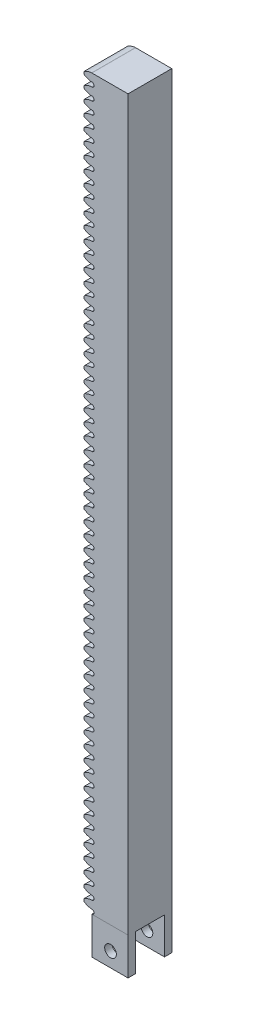
SolidWorks part; units mm, degrees
material "Plain Carbon Steel"
ref_plane "Front Plane" through (0, 0, 0) normal (0, 0, 1) x (1, 0, 0)
ref_plane "Top Plane" through (0, 0, 0) normal (0, 1, 0) x (1, 0, 0)
ref_plane "Right Plane" through (0, 0, 0) normal (1, 0, 0) x (0, 0, -1)
sketch "Sketch1" plane through (0, 0, 0) normal (0, 1, 0) x (1, 0, 0)
  line L1 (-12.4, -15) -> (12.4, -15)
  line L2 (-12.4, -15) -> (-12.4, 15)
  line L3 (-12.4, 15) -> (12.4, 15)
  line L4 (12.4, -15) -> (12.4, 15)
  line L5 (-12.4, -15) -> (12.4, 15) construction
  line L6 (-12.4, 15) -> (12.4, -15) construction
  point P0 (0, 0)
  dimension "D1" = 30
  dimension "D2" = 24.8
extrude "Boss-Extrude1" add sketch "Sketch1" along normal mid plane 525
sketch "do not delete" plane through (0, 0, 0) normal (0, 0, 1) x (1, 0, 0)
  circle A0 centre (-81.0597, 209.1285) radius 17.5
  line B0 (-46.1597, 207.5204) -> (-46.1597, 210.7365)
  line B1 (-50.1652, 211.8014) -> (-50.2795, 211.7916)
  line B2 (-50.776, 215.245) -> (-50.6636, 215.2677)
  line B3 (-52.1697, 220.3971) -> (-52.2766, 220.3555)
  line B4 (-53.726, 223.5291) -> (-53.6245, 223.5826)
  line B5 (-56.5147, 228.0799) -> (-56.6056, 228.0098)
  line B6 (-58.8903, 230.6466) -> (-58.808, 230.7265)
  line B7 (-62.8482, 234.2273) -> (-62.9156, 234.1345)
  line B8 (-65.8507, 236.0207) -> (-65.7942, 236.1206)
  line B9 (-70.657, 238.3414) -> (-70.6956, 238.2334)
  line B10 (-74.0432, 239.2163) -> (-74.0172, 239.328)
  line B11 (-79.3087, 240.0888) -> (-79.3152, 239.9743)
  line B12 (-82.8041, 239.9743) -> (-82.8106, 240.0888)
  line B13 (-88.1021, 239.328) -> (-88.0761, 239.2163)
  line B14 (-91.4237, 238.2334) -> (-91.4623, 238.3414)
  line B15 (-96.3251, 236.1206) -> (-96.2686, 236.0207)
  line B16 (-99.2037, 234.1345) -> (-99.2711, 234.2273)
  line B17 (-103.3113, 230.7265) -> (-103.229, 230.6466)
  line B18 (-105.5137, 228.0098) -> (-105.6046, 228.0799)
  line B19 (-108.4948, 223.5826) -> (-108.3933, 223.5291)
  line B20 (-109.8427, 220.3555) -> (-109.9496, 220.3971)
  line B21 (-111.4557, 215.2677) -> (-111.3433, 215.245)
  line B22 (-111.8398, 211.7916) -> (-111.9541, 211.8014)
  line B23 (-111.9541, 206.4555) -> (-111.8398, 206.4653)
  line B24 (-111.3433, 203.012) -> (-111.4557, 202.9892)
  line B25 (-109.9496, 197.8598) -> (-109.8427, 197.9014)
  line B26 (-108.3933, 194.7278) -> (-108.4948, 194.6743)
  line B27 (-105.6046, 190.177) -> (-105.5137, 190.2471)
  line B28 (-103.229, 187.6104) -> (-103.3113, 187.5304)
  line B29 (-99.2711, 184.0296) -> (-99.2037, 184.1224)
  line B30 (-96.2686, 182.2362) -> (-96.3251, 182.1363)
  line B31 (-91.4623, 179.9155) -> (-91.4237, 180.0236)
  line B32 (-88.0761, 179.0406) -> (-88.1021, 178.9289)
  line B33 (-82.8106, 178.1681) -> (-82.8041, 178.2826)
  line B34 (-79.3152, 178.2826) -> (-79.3087, 178.1681)
  line B35 (-74.0172, 178.9289) -> (-74.0432, 179.0406)
  line B36 (-70.6956, 180.0236) -> (-70.657, 179.9155)
  line B37 (-65.7942, 182.1363) -> (-65.8507, 182.2362)
  line B38 (-62.9156, 184.1224) -> (-62.8482, 184.0296)
  line B39 (-58.808, 187.5304) -> (-58.8903, 187.6104)
  line B40 (-56.6056, 190.2471) -> (-56.5147, 190.177)
  line B41 (-53.6245, 194.6743) -> (-53.726, 194.7278)
  line B42 (-52.2766, 197.9014) -> (-52.1697, 197.8598)
  line B43 (-50.6636, 202.9892) -> (-50.776, 203.012)
  line B44 (-50.2795, 206.4653) -> (-50.1652, 206.4555)
  arc B45 (-51.988, 213.1554) -> (-50.2795, 211.7916) centre (-50.4155, 213.3733) ccw
  arc B46 (-51.988, 213.1554) -> (-52.0311, 213.455) centre (-81.0597, 209.1285) ccw
  arc B47 (-50.776, 215.245) -> (-52.0311, 213.455) centre (-50.461, 213.6891) ccw
  arc B48 (-46.2345, 218.2505) -> (-46.8312, 220.2824) centre (-81.0597, 209.1285) ccw
  arc B49 (-54.3002, 221.1827) -> (-52.2766, 220.3555) centre (-52.8527, 221.8348) ccw
  arc B50 (-54.3002, 221.1827) -> (-54.4259, 221.4581) centre (-81.0597, 209.1285) ccw
  arc B51 (-53.726, 223.5291) -> (-54.4259, 221.4581) centre (-52.9853, 222.125) ccw
  arc B52 (-50.2152, 227.6923) -> (-51.3601, 229.4739) centre (-81.0597, 209.1285) ccw
  arc B53 (-58.7802, 228.2335) -> (-56.6056, 228.0098) centre (-57.5751, 229.2669) ccw
  arc B54 (-58.7802, 228.2335) -> (-58.9784, 228.4622) centre (-81.0597, 209.1285) ccw
  arc B55 (-58.8903, 230.6466) -> (-58.9784, 228.4622) centre (-57.784, 229.508) ccw
  arc B56 (-56.6946, 235.6303) -> (-58.2951, 237.0171) centre (-81.0597, 209.1285) ccw
  arc B57 (-65.0652, 233.7364) -> (-62.9156, 234.1345) centre (-64.2, 235.0675) ccw
  arc B58 (-65.0652, 233.7364) -> (-65.3198, 233.9001) centre (-81.0597, 209.1285) ccw
  arc B59 (-65.8507, 236.0207) -> (-65.3198, 233.9001) centre (-64.4684, 235.24) ccw
  arc B60 (-65.148, 241.4212) -> (-67.0744, 242.3009) centre (-81.0597, 209.1285) ccw
  arc B61 (-72.6459, 237.2458) -> (-70.6956, 238.2334) centre (-72.1908, 238.7667) ccw
  arc B62 (-72.6459, 237.2458) -> (-72.9363, 237.3311) centre (-81.0597, 209.1285) ccw
  arc B63 (-74.0432, 239.2163) -> (-72.9363, 237.3311) centre (-72.497, 238.8566) ccw
  arc B64 (-74.8904, 244.5959) -> (-76.9866, 244.8973) centre (-81.0597, 209.1285) ccw
  arc B65 (-80.9083, 238.4773) -> (-79.3152, 239.9743) centre (-80.9001, 240.0648) ccw
  arc B66 (-80.9083, 238.4773) -> (-81.211, 238.4773) centre (-81.0597, 209.1285) ccw
  arc B67 (-82.8041, 239.9743) -> (-81.211, 238.4773) centre (-81.2192, 240.0648) ccw
  arc B68 (-85.1327, 244.8973) -> (-87.2289, 244.5959) centre (-81.0597, 209.1285) ccw
  arc B69 (-89.183, 237.3311) -> (-88.0761, 239.2163) centre (-89.6223, 238.8566) ccw
  arc B70 (-89.183, 237.3311) -> (-89.4734, 237.2458) centre (-81.0597, 209.1285) ccw
  arc B71 (-91.4237, 238.2334) -> (-89.4734, 237.2458) centre (-89.9285, 238.7667) ccw
  arc B72 (-95.0449, 242.3009) -> (-96.9713, 241.4212) centre (-81.0597, 209.1285) ccw
  arc B73 (-96.7995, 233.9001) -> (-96.2686, 236.0207) centre (-97.6509, 235.24) ccw
  arc B74 (-96.7995, 233.9001) -> (-97.0541, 233.7364) centre (-81.0597, 209.1285) ccw
  arc B75 (-99.2037, 234.1345) -> (-97.0541, 233.7364) centre (-97.9193, 235.0675) ccw
  arc B76 (-103.8242, 237.0171) -> (-105.4247, 235.6303) centre (-81.0597, 209.1285) ccw
  arc B77 (-103.1409, 228.4622) -> (-103.229, 230.6466) centre (-104.3353, 229.508) ccw
  arc B78 (-103.1409, 228.4622) -> (-103.3391, 228.2335) centre (-81.0597, 209.1285) ccw
  arc B79 (-105.5137, 228.0098) -> (-103.3391, 228.2335) centre (-104.5442, 229.2669) ccw
  arc B80 (-110.7592, 229.4739) -> (-111.9041, 227.6923) centre (-81.0597, 209.1285) ccw
  arc B81 (-107.6934, 221.4581) -> (-108.3933, 223.5291) centre (-109.134, 222.125) ccw
  arc B82 (-107.6934, 221.4581) -> (-107.8191, 221.1827) centre (-81.0597, 209.1285) ccw
  arc B83 (-109.8427, 220.3555) -> (-107.8191, 221.1827) centre (-109.2666, 221.8348) ccw
  arc B84 (-115.2881, 220.2824) -> (-115.8848, 218.2505) centre (-81.0597, 209.1285) ccw
  arc B85 (-110.0882, 213.455) -> (-111.3433, 215.245) centre (-111.6584, 213.6891) ccw
  arc B86 (-110.0882, 213.455) -> (-110.1313, 213.1554) centre (-81.0597, 209.1285) ccw
  arc B87 (-111.8398, 211.7916) -> (-110.1313, 213.1554) centre (-111.7038, 213.3733) ccw
  arc B88 (-117.0441, 210.1873) -> (-117.0441, 208.0696) centre (-81.0597, 209.1285) ccw
  arc B89 (-110.1313, 205.1015) -> (-111.8398, 206.4653) centre (-111.7038, 204.8837) ccw
  arc B90 (-110.1313, 205.1015) -> (-110.0882, 204.8019) centre (-81.0597, 209.1285) ccw
  arc B91 (-111.3433, 203.012) -> (-110.0882, 204.8019) centre (-111.6584, 204.5679) ccw
  arc B92 (-115.8848, 200.0065) -> (-115.2881, 197.9745) centre (-81.0597, 209.1285) ccw
  arc B93 (-107.8191, 197.0742) -> (-109.8427, 197.9014) centre (-109.2666, 196.4222) ccw
  arc B94 (-107.8191, 197.0742) -> (-107.6934, 196.7989) centre (-81.0597, 209.1285) ccw
  arc B95 (-108.3933, 194.7278) -> (-107.6934, 196.7989) centre (-109.134, 196.132) ccw
  arc B96 (-111.9041, 190.5646) -> (-110.7592, 188.783) centre (-81.0597, 209.1285) ccw
  arc B97 (-103.3391, 190.0235) -> (-105.5137, 190.2471) centre (-104.5442, 188.9901) ccw
  arc B98 (-103.3391, 190.0235) -> (-103.1409, 189.7947) centre (-81.0597, 209.1285) ccw
  arc B99 (-103.229, 187.6104) -> (-103.1409, 189.7947) centre (-104.3353, 188.7489) ccw
  arc B100 (-105.4247, 182.6267) -> (-103.8242, 181.2398) centre (-81.0597, 209.1285) ccw
  arc B101 (-97.0541, 184.5205) -> (-99.2037, 184.1224) centre (-97.9193, 183.1894) ccw
  arc B102 (-97.0541, 184.5205) -> (-96.7995, 184.3569) centre (-81.0597, 209.1285) ccw
  arc B103 (-96.2686, 182.2362) -> (-96.7995, 184.3569) centre (-97.6509, 183.017) ccw
  arc B104 (-96.9713, 176.8358) -> (-95.0449, 175.956) centre (-81.0597, 209.1285) ccw
  arc B105 (-89.4734, 181.0111) -> (-91.4237, 180.0236) centre (-89.9285, 179.4903) ccw
  arc B106 (-89.4734, 181.0111) -> (-89.183, 180.9258) centre (-81.0597, 209.1285) ccw
  arc B107 (-88.0761, 179.0406) -> (-89.183, 180.9258) centre (-89.6223, 179.4004) ccw
  arc B108 (-87.2289, 173.661) -> (-85.1327, 173.3596) centre (-81.0597, 209.1285) ccw
  arc B109 (-81.211, 179.7797) -> (-82.8041, 178.2826) centre (-81.2192, 178.1922) ccw
  arc B110 (-81.211, 179.7797) -> (-80.9083, 179.7797) centre (-81.0597, 209.1285) ccw
  arc B111 (-79.3152, 178.2826) -> (-80.9083, 179.7797) centre (-80.9001, 178.1922) ccw
  arc B112 (-76.9866, 173.3596) -> (-74.8904, 173.661) centre (-81.0597, 209.1285) ccw
  arc B113 (-72.9363, 180.9258) -> (-74.0432, 179.0406) centre (-72.497, 179.4004) ccw
  arc B114 (-72.9363, 180.9258) -> (-72.6459, 181.0111) centre (-81.0597, 209.1285) ccw
  arc B115 (-70.6956, 180.0236) -> (-72.6459, 181.0111) centre (-72.1908, 179.4903) ccw
  arc B116 (-67.0744, 175.956) -> (-65.148, 176.8358) centre (-81.0597, 209.1285) ccw
  arc B117 (-65.3198, 184.3569) -> (-65.8507, 182.2362) centre (-64.4684, 183.017) ccw
  arc B118 (-65.3198, 184.3569) -> (-65.0652, 184.5205) centre (-81.0597, 209.1285) ccw
  arc B119 (-62.9156, 184.1224) -> (-65.0652, 184.5205) centre (-64.2, 183.1894) ccw
  arc B120 (-58.2951, 181.2398) -> (-56.6946, 182.6267) centre (-81.0597, 209.1285) ccw
  arc B121 (-58.9784, 189.7947) -> (-58.8903, 187.6104) centre (-57.784, 188.7489) ccw
  arc B122 (-58.9784, 189.7947) -> (-58.7802, 190.0235) centre (-81.0597, 209.1285) ccw
  arc B123 (-56.6056, 190.2471) -> (-58.7802, 190.0235) centre (-57.5751, 188.9901) ccw
  arc B124 (-51.3601, 188.783) -> (-50.2152, 190.5646) centre (-81.0597, 209.1285) ccw
  arc B125 (-54.4259, 196.7989) -> (-53.726, 194.7278) centre (-52.9853, 196.132) ccw
  arc B126 (-54.4259, 196.7989) -> (-54.3002, 197.0742) centre (-81.0597, 209.1285) ccw
  arc B127 (-52.2766, 197.9014) -> (-54.3002, 197.0742) centre (-52.8527, 196.4222) ccw
  arc B128 (-46.8312, 197.9745) -> (-46.2345, 200.0065) centre (-81.0597, 209.1285) ccw
  arc B129 (-52.0311, 204.8019) -> (-50.776, 203.012) centre (-50.461, 204.5679) ccw
  arc B130 (-52.0311, 204.8019) -> (-51.988, 205.1015) centre (-81.0597, 209.1285) ccw
  arc B131 (-50.2795, 206.4653) -> (-51.988, 205.1015) centre (-50.4155, 204.8837) ccw
  spline B132 degree 5 poles (-46.1597, 210.7365) (-46.3289, 210.8147) (-46.5562, 210.9157) (-46.8422, 211.0359) (-47.202, 211.1762) (-47.6072, 211.3178) (-47.8704, 211.4029) (-48.1342, 211.4814) (-48.3544, 211.5414) (-48.5602, 211.5938) (-48.7368, 211.6345) (-48.9429, 211.6775) (-49.105, 211.7084) (-49.2819, 211.7383) (-49.4441, 211.7612) (-49.6063, 211.7784) (-49.7684, 211.7934) (-49.9157, 211.8055) (-50.0333, 211.809) (-50.1066, 211.8065) (-50.1652, 211.8014) knots 0 0 0 0 0 0 0.168282 0.225425 0.282568 0.353997 0.396854 0.425425 0.482568 0.496854 0.553997 0.568282 0.625425 0.639711 0.668282 0.711139 0.725425 0.782568 0.782568 0.782568 0.782568 0.782568 0.782568 weights 1 1 1 1 1 1 1 1 1 1 1 1 1 1 1 1 1 1 1 1 1
  spline B133 degree 5 poles (-50.6636, 215.2677) (-50.606, 215.2794) (-50.5349, 215.2977) (-50.437, 215.3296) (-50.3127, 215.3765) (-50.175, 215.4309) (-50.0378, 215.4866) (-49.9015, 215.5458) (-49.7396, 215.6223) (-49.579, 215.7033) (-49.3929, 215.8014) (-49.2082, 215.9037) (-49.0123, 216.0194) (-48.818, 216.139) (-48.574, 216.2965) (-48.3074, 216.4787) (-48.0315, 216.6776) (-47.7101, 216.9237) (-47.3817, 217.1908) (-47.0702, 217.4583) (-46.7755, 217.7249) (-46.5433, 217.945) (-46.3826, 218.1022) (-46.28, 218.2047) (-46.2345, 218.2505) knots 0 0 0 0 0 0 0.057143 0.071429 0.1 0.128571 0.142857 0.2 0.214286 0.271429 0.3 0.342857 0.4 0.428571 0.485714 0.571429 0.642857 0.714286 0.8 0.871429 0.942857 1 1 1 1 1 1 weights 1 1 1 1 1 1 1 1 1 1 1 1 1 1 1 1 1 1 1 1 1 1 1 1 1
  spline B134 degree 5 poles (-46.8312, 220.2824) (-47.0359, 220.3277) (-47.3034, 220.3829) (-47.6333, 220.4444) (-48.0409, 220.5098) (-48.525, 220.5717) (-48.8674, 220.6073) (-49.2241, 220.6357) (-49.5637, 220.6534) (-49.8556, 220.6612) (-50.1308, 220.6622) (-50.359, 220.6578) (-50.5712, 220.65) (-50.7521, 220.6394) (-50.962, 220.6226) (-51.1263, 220.6065) (-51.3044, 220.5854) (-51.4665, 220.5617) (-51.6269, 220.5325) (-51.7867, 220.5013) (-51.9314, 220.4713) (-52.0452, 220.4416) (-52.1149, 220.4185) (-52.1697, 220.3971) knots 0 0 0 0 0 0 0.185714 0.242857 0.3 0.371429 0.442857 0.5 0.571429 0.614286 0.642857 0.7 0.714286 0.771429 0.785714 0.842857 0.857143 0.885714 0.928571 0.942857 1 1 1 1 1 1 weights 1 1 1 1 1 1 1 1 1 1 1 1 1 1 1 1 1 1 1 1 1 1 1 1
  spline B135 degree 5 poles (-53.6245, 223.5826) (-53.5725, 223.6101) (-53.5094, 223.6476) (-53.4245, 223.7058) (-53.3184, 223.7858) (-53.2017, 223.8768) (-53.0856, 223.9689) (-52.9716, 224.0641) (-52.8378, 224.1831) (-52.7065, 224.3061) (-52.5556, 224.4527) (-52.4072, 224.6029) (-52.2519, 224.769) (-52.0991, 224.9386) (-51.9093, 225.1584) (-51.7049, 225.4083) (-51.4962, 225.6769) (-51.2572, 226.0036) (-51.0173, 226.3524) (-50.7939, 226.6968) (-50.5861, 227.0356) (-50.4254, 227.3122) (-50.3155, 227.5084) (-50.2459, 227.6356) (-50.2152, 227.6923) knots 0 0 0 0 0 0 0.057143 0.071429 0.1 0.128571 0.142857 0.2 0.214286 0.271429 0.3 0.342857 0.4 0.428571 0.485714 0.571429 0.642857 0.714286 0.8 0.871429 0.942857 1 1 1 1 1 1 weights 1 1 1 1 1 1 1 1 1 1 1 1 1 1 1 1 1 1 1 1 1 1 1 1 1
  spline B136 degree 5 poles (-51.3601, 229.4739) (-51.5693, 229.4597) (-51.8415, 229.4373) (-52.1754, 229.4033) (-52.5849, 229.3513) (-53.0668, 229.2742) (-53.4054, 229.2119) (-53.7556, 229.1387) (-54.0864, 229.06) (-54.3687, 228.9853) (-54.6331, 228.9087) (-54.8508, 228.8401) (-55.0522, 228.7729) (-55.2228, 228.7118) (-55.4195, 228.6365) (-55.5725, 228.5748) (-55.7375, 228.5043) (-55.8863, 228.4359) (-56.0321, 228.3627) (-56.1766, 228.2877) (-56.307, 228.2182) (-56.4078, 228.1576) (-56.4681, 228.1158) (-56.5147, 228.0799) knots 0 0 0 0 0 0 0.185714 0.242857 0.3 0.371429 0.442857 0.5 0.571429 0.614286 0.642857 0.7 0.714286 0.771429 0.785714 0.842857 0.857143 0.885714 0.928571 0.942857 1 1 1 1 1 1 weights 1 1 1 1 1 1 1 1 1 1 1 1 1 1 1 1 1 1 1 1 1 1 1 1
  spline B137 degree 5 poles (-58.808, 230.7265) (-58.7658, 230.7675) (-58.7159, 230.8213) (-58.6508, 230.901) (-58.5716, 231.0077) (-58.4852, 231.1279) (-58.3998, 231.2489) (-58.3172, 231.3724) (-58.2224, 231.5243) (-58.1311, 231.6793) (-58.0276, 231.8624) (-57.9275, 232.0484) (-57.8252, 232.2515) (-57.7264, 232.4573) (-57.6063, 232.7217) (-57.4806, 233.0191) (-57.356, 233.3356) (-57.2187, 233.7164) (-57.0868, 234.1187) (-56.9694, 234.5121) (-56.8656, 234.8956) (-56.7892, 235.2063) (-56.739, 235.4255) (-56.7081, 235.5672) (-56.6946, 235.6303) knots 0 0 0 0 0 0 0.057143 0.071429 0.1 0.128571 0.142857 0.2 0.214286 0.271429 0.3 0.342857 0.4 0.428571 0.485714 0.571429 0.642857 0.714286 0.8 0.871429 0.942857 1 1 1 1 1 1 weights 1 1 1 1 1 1 1 1 1 1 1 1 1 1 1 1 1 1 1 1 1 1 1 1 1
  spline B138 degree 5 poles (-58.2951, 237.0171) (-58.4918, 236.9445) (-58.7467, 236.8463) (-59.0575, 236.7196) (-59.4358, 236.5544) (-59.8764, 236.3447) (-60.1838, 236.1895) (-60.4992, 236.0206) (-60.7944, 235.8518) (-61.0442, 235.7006) (-61.2763, 235.5527) (-61.4658, 235.4256) (-61.6402, 235.3043) (-61.7866, 235.1976) (-61.9541, 235.0699) (-62.0836, 234.9676) (-62.2221, 234.8535) (-62.3456, 234.746) (-62.4648, 234.6347) (-62.5823, 234.522) (-62.6878, 234.4186) (-62.7675, 234.332) (-62.8136, 234.2749) (-62.8482, 234.2273) knots 0 0 0 0 0 0 0.185714 0.242857 0.3 0.371429 0.442857 0.5 0.571429 0.614286 0.642857 0.7 0.714286 0.771429 0.785714 0.842857 0.857143 0.885714 0.928571 0.942857 1 1 1 1 1 1 weights 1 1 1 1 1 1 1 1 1 1 1 1 1 1 1 1 1 1 1 1 1 1 1 1
  spline B139 degree 5 poles (-65.7942, 236.1206) (-65.7653, 236.1719) (-65.7325, 236.2375) (-65.6926, 236.3324) (-65.6466, 236.4571) (-65.5976, 236.5967) (-65.5498, 236.7369) (-65.5053, 236.8787) (-65.4571, 237.0512) (-65.4131, 237.2255) (-65.3654, 237.4304) (-65.3218, 237.637) (-65.2809, 237.8608) (-65.244, 238.086) (-65.2033, 238.3736) (-65.1664, 238.6943) (-65.1361, 239.0331) (-65.1116, 239.4372) (-65.0984, 239.8603) (-65.0966, 240.2708) (-65.105, 240.6681) (-65.1193, 240.9877) (-65.1329, 241.2122) (-65.1432, 241.3568) (-65.148, 241.4212) knots 0 0 0 0 0 0 0.057143 0.071429 0.1 0.128571 0.142857 0.2 0.214286 0.271429 0.3 0.342857 0.4 0.428571 0.485714 0.571429 0.642857 0.714286 0.8 0.871429 0.942857 1 1 1 1 1 1 weights 1 1 1 1 1 1 1 1 1 1 1 1 1 1 1 1 1 1 1 1 1 1 1 1 1
  spline B140 degree 5 poles (-67.0744, 242.3009) (-67.2427, 242.1759) (-67.4595, 242.0098) (-67.7221, 241.8007) (-68.0384, 241.5356) (-68.4022, 241.2102) (-68.6534, 240.9748) (-68.9084, 240.7238) (-69.1441, 240.4787) (-69.3412, 240.2633) (-69.5222, 240.0559) (-69.6683, 239.8806) (-69.8014, 239.7151) (-69.9118, 239.5714) (-70.0366, 239.4018) (-70.132, 239.2671) (-70.2327, 239.1187) (-70.3209, 238.9806) (-70.4039, 238.8403) (-70.4849, 238.6991) (-70.5571, 238.5701) (-70.6091, 238.4646) (-70.6373, 238.3968) (-70.657, 238.3414) knots 0 0 0 0 0 0 0.185714 0.242857 0.3 0.371429 0.442857 0.5 0.571429 0.614286 0.642857 0.7 0.714286 0.771429 0.785714 0.842857 0.857143 0.885714 0.928571 0.942857 1 1 1 1 1 1 weights 1 1 1 1 1 1 1 1 1 1 1 1 1 1 1 1 1 1 1 1 1 1 1 1
  spline B141 degree 5 poles (-74.0172, 239.328) (-74.0038, 239.3853) (-73.9909, 239.4576) (-73.9793, 239.5599) (-73.9703, 239.6924) (-73.9626, 239.8402) (-73.9562, 239.9882) (-73.9535, 240.1368) (-73.9558, 240.3158) (-73.9628, 240.4955) (-73.9747, 240.7056) (-73.9911, 240.9161) (-74.0149, 241.1423) (-74.043, 241.3688) (-74.0849, 241.6562) (-74.1399, 241.9743) (-74.2062, 242.308) (-74.2966, 242.7025) (-74.4031, 243.1123) (-74.5171, 243.5067) (-74.6371, 243.8855) (-74.7408, 244.1881) (-74.8171, 244.3997) (-74.8677, 244.5356) (-74.8904, 244.5959) knots 0 0 0 0 0 0 0.057143 0.071429 0.1 0.128571 0.142857 0.2 0.214286 0.271429 0.3 0.342857 0.4 0.428571 0.485714 0.571429 0.642857 0.714286 0.8 0.871429 0.942857 1 1 1 1 1 1 weights 1 1 1 1 1 1 1 1 1 1 1 1 1 1 1 1 1 1 1 1 1 1 1 1 1
  spline B142 degree 5 poles (-76.9866, 244.8973) (-77.1129, 244.7299) (-77.2742, 244.5095) (-77.4672, 244.2349) (-77.696, 243.8914) (-77.9534, 243.4767) (-78.128, 243.18) (-78.302, 242.8674) (-78.4592, 242.5658) (-78.5876, 242.3036) (-78.7028, 242.0536) (-78.7936, 241.8442) (-78.8747, 241.648) (-78.9402, 241.479) (-79.0121, 241.2811) (-79.0657, 241.125) (-79.1205, 240.9542) (-79.1662, 240.7969) (-79.2064, 240.6388) (-79.2443, 240.4805) (-79.2772, 240.3364) (-79.2974, 240.2205) (-79.3053, 240.1476) (-79.3087, 240.0888) knots 0 0 0 0 0 0 0.185714 0.242857 0.3 0.371429 0.442857 0.5 0.571429 0.614286 0.642857 0.7 0.714286 0.771429 0.785714 0.842857 0.857143 0.885714 0.928571 0.942857 1 1 1 1 1 1 weights 1 1 1 1 1 1 1 1 1 1 1 1 1 1 1 1 1 1 1 1 1 1 1 1
  spline B143 degree 5 poles (-82.8106, 240.0888) (-82.814, 240.1476) (-82.8219, 240.2205) (-82.8396, 240.3219) (-82.8683, 240.4517) (-82.9026, 240.5956) (-82.9381, 240.7394) (-82.9774, 240.8828) (-83.0301, 241.0539) (-83.0874, 241.2244) (-83.158, 241.4225) (-83.233, 241.6199) (-83.3196, 241.8303) (-83.4104, 242.0397) (-83.5315, 242.3036) (-83.6739, 242.5934) (-83.8316, 242.8948) (-84.0294, 243.2479) (-84.2471, 243.6111) (-84.4675, 243.9574) (-84.6894, 244.287) (-84.8742, 244.5482) (-85.007, 244.7297) (-85.0938, 244.8458) (-85.1327, 244.8973) knots 0 0 0 0 0 0 0.057143 0.071429 0.1 0.128571 0.142857 0.2 0.214286 0.271429 0.3 0.342857 0.4 0.428571 0.485714 0.571429 0.642857 0.714286 0.8 0.871429 0.942857 1 1 1 1 1 1 weights 1 1 1 1 1 1 1 1 1 1 1 1 1 1 1 1 1 1 1 1 1 1 1 1 1
  spline B144 degree 5 poles (-87.2289, 244.5959) (-87.3029, 244.3997) (-87.3955, 244.1428) (-87.5033, 243.825) (-87.6261, 243.4309) (-87.7562, 242.9605) (-87.8402, 242.6266) (-87.9191, 242.2776) (-87.9849, 241.944) (-88.0342, 241.6562) (-88.0744, 241.3839) (-88.1025, 241.1574) (-88.125, 240.9463) (-88.1402, 240.7657) (-88.1534, 240.5555) (-88.1609, 240.3907) (-88.1654, 240.2113) (-88.1649, 240.0475) (-88.1589, 239.8846) (-88.1507, 239.722) (-88.1417, 239.5745) (-88.1284, 239.4576) (-88.1155, 239.3853) (-88.1021, 239.328) knots 0 0 0 0 0 0 0.185714 0.242857 0.3 0.371429 0.442857 0.5 0.571429 0.614286 0.642857 0.7 0.714286 0.771429 0.785714 0.842857 0.857143 0.885714 0.928571 0.942857 1 1 1 1 1 1 weights 1 1 1 1 1 1 1 1 1 1 1 1 1 1 1 1 1 1 1 1 1 1 1 1
  spline B145 degree 5 poles (-91.4623, 238.3414) (-91.482, 238.3968) (-91.5102, 238.4646) (-91.5557, 238.5569) (-91.6199, 238.6733) (-91.6933, 238.8018) (-91.7679, 238.9297) (-91.8459, 239.0562) (-91.9447, 239.2056) (-92.0477, 239.353) (-92.1713, 239.5232) (-92.2989, 239.6915) (-92.4412, 239.8689) (-92.5873, 240.0443) (-92.7779, 240.2634) (-92.9962, 240.5013) (-93.2324, 240.7461) (-93.5217, 241.0292) (-93.8328, 241.3163) (-94.1419, 241.5864) (-94.4477, 241.8402) (-94.6986, 242.0387) (-94.8771, 242.1755) (-94.9931, 242.2624) (-95.0449, 242.3009) knots 0 0 0 0 0 0 0.057143 0.071429 0.1 0.128571 0.142857 0.2 0.214286 0.271429 0.3 0.342857 0.4 0.428571 0.485714 0.571429 0.642857 0.714286 0.8 0.871429 0.942857 1 1 1 1 1 1 weights 1 1 1 1 1 1 1 1 1 1 1 1 1 1 1 1 1 1 1 1 1 1 1 1 1
  spline B146 degree 5 poles (-96.9713, 241.4212) (-96.987, 241.2121) (-97.0035, 240.9395) (-97.0174, 240.6041) (-97.0242, 240.1914) (-97.0166, 239.7034) (-97.0031, 239.3594) (-96.9804, 239.0023) (-96.9496, 238.6637) (-96.9158, 238.3736) (-96.8776, 238.1011) (-96.8408, 237.8758) (-96.8029, 237.6669) (-96.7667, 237.4893) (-96.7201, 237.284) (-96.6808, 237.1237) (-96.6346, 236.9503) (-96.588, 236.7933) (-96.5364, 236.6386) (-96.4827, 236.4849) (-96.4324, 236.346) (-96.3868, 236.2375) (-96.354, 236.1719) (-96.3251, 236.1206) knots 0 0 0 0 0 0 0.185714 0.242857 0.3 0.371429 0.442857 0.5 0.571429 0.614286 0.642857 0.7 0.714286 0.771429 0.785714 0.842857 0.857143 0.885714 0.928571 0.942857 1 1 1 1 1 1 weights 1 1 1 1 1 1 1 1 1 1 1 1 1 1 1 1 1 1 1 1 1 1 1 1
  spline B147 degree 5 poles (-99.2711, 234.2273) (-99.3057, 234.2749) (-99.3518, 234.332) (-99.4215, 234.4078) (-99.5158, 234.5014) (-99.6225, 234.604) (-99.7301, 234.7057) (-99.8406, 234.8051) (-99.9775, 234.9206) (-100.1179, 235.033) (-100.2844, 235.1615) (-100.4542, 235.287) (-100.6408, 235.4171) (-100.8304, 235.5443) (-101.075, 235.7008) (-101.3514, 235.8675) (-101.647, 236.0359) (-102.0044, 236.226) (-102.3838, 236.4138) (-102.7565, 236.586) (-103.1214, 236.7433) (-103.418, 236.8631) (-103.6279, 236.944) (-103.7637, 236.9948) (-103.8242, 237.0171) knots 0 0 0 0 0 0 0.057143 0.071429 0.1 0.128571 0.142857 0.2 0.214286 0.271429 0.3 0.342857 0.4 0.428571 0.485714 0.571429 0.642857 0.714286 0.8 0.871429 0.942857 1 1 1 1 1 1 weights 1 1 1 1 1 1 1 1 1 1 1 1 1 1 1 1 1 1 1 1 1 1 1 1 1
  spline B148 degree 5 poles (-105.4247, 235.6303) (-105.3809, 235.4252) (-105.3199, 235.159) (-105.2387, 234.8333) (-105.129, 234.4354) (-104.9842, 233.9694) (-104.8743, 233.6431) (-104.752, 233.3068) (-104.627, 232.9906) (-104.5129, 232.7218) (-104.3994, 232.471) (-104.3006, 232.2653) (-104.2054, 232.0755) (-104.1206, 231.9154) (-104.0181, 231.7314) (-103.9352, 231.5887) (-103.842, 231.4354) (-103.7531, 231.2978) (-103.6599, 231.164) (-103.5651, 231.0316) (-103.4778, 230.9124) (-103.4034, 230.8213) (-103.3535, 230.7675) (-103.3113, 230.7265) knots 0 0 0 0 0 0 0.185714 0.242857 0.3 0.371429 0.442857 0.5 0.571429 0.614286 0.642857 0.7 0.714286 0.771429 0.785714 0.842857 0.857143 0.885714 0.928571 0.942857 1 1 1 1 1 1 weights 1 1 1 1 1 1 1 1 1 1 1 1 1 1 1 1 1 1 1 1 1 1 1 1
  spline B149 degree 5 poles (-105.6046, 228.0799) (-105.6512, 228.1158) (-105.7115, 228.1576) (-105.7997, 228.2106) (-105.9166, 228.2739) (-106.0478, 228.3423) (-106.1798, 228.4096) (-106.3138, 228.4738) (-106.4777, 228.546) (-106.644, 228.6143) (-106.84, 228.6907) (-107.0383, 228.7633) (-107.254, 228.8356) (-107.4717, 228.9042) (-107.7505, 228.9854) (-108.0627, 229.0676) (-108.3938, 229.1458) (-108.7902, 229.2275) (-109.2072, 229.3009) (-109.6133, 229.361) (-110.0077, 229.4092) (-110.3261, 229.4406) (-110.5502, 229.4591) (-110.6948, 229.4695) (-110.7592, 229.4739) knots 0 0 0 0 0 0 0.057143 0.071429 0.1 0.128571 0.142857 0.2 0.214286 0.271429 0.3 0.342857 0.4 0.428571 0.485714 0.571429 0.642857 0.714286 0.8 0.871429 0.942857 1 1 1 1 1 1 weights 1 1 1 1 1 1 1 1 1 1 1 1 1 1 1 1 1 1 1 1 1 1 1 1 1
  spline B150 degree 5 poles (-111.9041, 227.6923) (-111.8043, 227.5079) (-111.6709, 227.2697) (-111.5012, 226.98) (-111.2838, 226.6291) (-111.0135, 226.2228) (-110.8162, 225.9407) (-110.6041, 225.6525) (-110.3951, 225.3843) (-110.2099, 225.1586) (-110.0304, 224.9499) (-109.8776, 224.7804) (-109.7328, 224.6251) (-109.6063, 224.4953) (-109.4561, 224.3477) (-109.3364, 224.2341) (-109.2038, 224.1133) (-109.0797, 224.0063) (-108.9526, 223.9042) (-108.8243, 223.8039) (-108.7069, 223.7141) (-108.6099, 223.6476) (-108.5468, 223.6101) (-108.4948, 223.5826) knots 0 0 0 0 0 0 0.185714 0.242857 0.3 0.371429 0.442857 0.5 0.571429 0.614286 0.642857 0.7 0.714286 0.771429 0.785714 0.842857 0.857143 0.885714 0.928571 0.942857 1 1 1 1 1 1 weights 1 1 1 1 1 1 1 1 1 1 1 1 1 1 1 1 1 1 1 1 1 1 1 1
  spline B151 degree 5 poles (-109.9496, 220.3971) (-110.0044, 220.4185) (-110.0741, 220.4416) (-110.1737, 220.4676) (-110.3036, 220.4954) (-110.4488, 220.524) (-110.5944, 220.5514) (-110.741, 220.5752) (-110.9186, 220.5984) (-111.0975, 220.6171) (-111.3071, 220.6351) (-111.5178, 220.6489) (-111.7451, 220.6576) (-111.9733, 220.662) (-112.2637, 220.6614) (-112.5864, 220.6522) (-112.9261, 220.6341) (-113.3295, 220.6008) (-113.7502, 220.5537) (-114.1568, 220.497) (-114.5489, 220.4321) (-114.8632, 220.3725) (-115.0834, 220.3271) (-115.2251, 220.2964) (-115.2881, 220.2824) knots 0 0 0 0 0 0 0.057143 0.071429 0.1 0.128571 0.142857 0.2 0.214286 0.271429 0.3 0.342857 0.4 0.428571 0.485714 0.571429 0.642857 0.714286 0.8 0.871429 0.942857 1 1 1 1 1 1 weights 1 1 1 1 1 1 1 1 1 1 1 1 1 1 1 1 1 1 1 1 1 1 1 1 1
  spline B152 degree 5 poles (-115.8848, 218.2505) (-115.737, 218.1016) (-115.5419, 217.9107) (-115.2975, 217.6805) (-114.99, 217.4051) (-114.6162, 217.0914) (-114.3474, 216.8763) (-114.0627, 216.6596) (-113.7866, 216.4611) (-113.5453, 216.2967) (-113.3143, 216.1471) (-113.1199, 216.0274) (-112.9372, 215.9192) (-112.7793, 215.8303) (-112.5936, 215.731) (-112.4467, 215.6557) (-112.2854, 215.5772) (-112.1363, 215.5095) (-111.9855, 215.4473) (-111.8342, 215.3872) (-111.6963, 215.3342) (-111.5845, 215.2977) (-111.5134, 215.2794) (-111.4557, 215.2677) knots 0 0 0 0 0 0 0.185714 0.242857 0.3 0.371429 0.442857 0.5 0.571429 0.614286 0.642857 0.7 0.714286 0.771429 0.785714 0.842857 0.857143 0.885714 0.928571 0.942857 1 1 1 1 1 1 weights 1 1 1 1 1 1 1 1 1 1 1 1 1 1 1 1 1 1 1 1 1 1 1 1
  spline B153 degree 5 poles (-111.9541, 211.8014) (-112.0127, 211.8065) (-112.086, 211.809) (-112.1889, 211.8059) (-112.3215, 211.7959) (-112.4688, 211.7825) (-112.6162, 211.7678) (-112.7637, 211.7493) (-112.9406, 211.7216) (-113.1174, 211.6891) (-113.3237, 211.6474) (-113.5297, 211.6012) (-113.7502, 211.5455) (-113.9704, 211.4854) (-114.2489, 211.4031) (-114.556, 211.3033) (-114.8768, 211.1902) (-115.2545, 211.0446) (-115.6449, 210.8809) (-116.019, 210.7119) (-116.3769, 210.5392) (-116.6617, 210.3935) (-116.8603, 210.2878) (-116.9876, 210.2185) (-117.0441, 210.1873) knots 0 0 0 0 0 0 0.057143 0.071429 0.1 0.128571 0.142857 0.2 0.214286 0.271429 0.3 0.342857 0.4 0.428571 0.485714 0.571429 0.642857 0.714286 0.8 0.871429 0.942857 1 1 1 1 1 1 weights 1 1 1 1 1 1 1 1 1 1 1 1 1 1 1 1 1 1 1 1 1 1 1 1 1
  spline B154 degree 5 poles (-117.0441, 208.0696) (-116.8604, 207.9684) (-116.6193, 207.8402) (-116.32, 207.6882) (-115.9474, 207.5106) (-115.5004, 207.3148) (-115.1818, 207.1842) (-114.8476, 207.0565) (-114.5268, 206.9438) (-114.2489, 206.8541) (-113.9851, 206.7756) (-113.7649, 206.7155) (-113.5591, 206.6632) (-113.3825, 206.6224) (-113.1764, 206.5794) (-113.0143, 206.5486) (-112.8374, 206.5186) (-112.6752, 206.4957) (-112.513, 206.4785) (-112.3509, 206.4635) (-112.2036, 206.4514) (-112.086, 206.4479) (-112.0127, 206.4505) (-111.9541, 206.4555) knots 0 0 0 0 0 0 0.185714 0.242857 0.3 0.371429 0.442857 0.5 0.571429 0.614286 0.642857 0.7 0.714286 0.771429 0.785714 0.842857 0.857143 0.885714 0.928571 0.942857 1 1 1 1 1 1 weights 1 1 1 1 1 1 1 1 1 1 1 1 1 1 1 1 1 1 1 1 1 1 1 1
  spline B155 degree 5 poles (-111.4557, 202.9892) (-111.5134, 202.9775) (-111.5845, 202.9593) (-111.6823, 202.9273) (-111.8066, 202.8804) (-111.9443, 202.826) (-112.0815, 202.7704) (-112.2178, 202.7111) (-112.3797, 202.6346) (-112.5403, 202.5536) (-112.7264, 202.4555) (-112.9111, 202.3532) (-113.107, 202.2376) (-113.3014, 202.1179) (-113.5453, 201.9604) (-113.8119, 201.7782) (-114.0878, 201.5793) (-114.4092, 201.3332) (-114.7376, 201.0661) (-115.0491, 200.7986) (-115.3438, 200.5321) (-115.576, 200.312) (-115.7367, 200.1547) (-115.8393, 200.0523) (-115.8848, 200.0065) knots 0 0 0 0 0 0 0.057143 0.071429 0.1 0.128571 0.142857 0.2 0.214286 0.271429 0.3 0.342857 0.4 0.428571 0.485714 0.571429 0.642857 0.714286 0.8 0.871429 0.942857 1 1 1 1 1 1 weights 1 1 1 1 1 1 1 1 1 1 1 1 1 1 1 1 1 1 1 1 1 1 1 1 1
  spline B156 degree 5 poles (-115.2881, 197.9745) (-115.0834, 197.9292) (-114.8159, 197.874) (-114.486, 197.8126) (-114.0784, 197.7471) (-113.5943, 197.6852) (-113.2519, 197.6496) (-112.8952, 197.6212) (-112.5556, 197.6036) (-112.2637, 197.5957) (-111.9885, 197.5947) (-111.7603, 197.5991) (-111.5481, 197.6069) (-111.3672, 197.6175) (-111.1573, 197.6344) (-110.9931, 197.6504) (-110.8149, 197.6715) (-110.6528, 197.6953) (-110.4924, 197.7244) (-110.3326, 197.7557) (-110.1879, 197.7856) (-110.0741, 197.8154) (-110.0044, 197.8385) (-109.9496, 197.8598) knots 0 0 0 0 0 0 0.185714 0.242857 0.3 0.371429 0.442857 0.5 0.571429 0.614286 0.642857 0.7 0.714286 0.771429 0.785714 0.842857 0.857143 0.885714 0.928571 0.942857 1 1 1 1 1 1 weights 1 1 1 1 1 1 1 1 1 1 1 1 1 1 1 1 1 1 1 1 1 1 1 1
  spline B157 degree 5 poles (-108.4948, 194.6743) (-108.5468, 194.6469) (-108.6099, 194.6093) (-108.6948, 194.5511) (-108.8009, 194.4711) (-108.9176, 194.3801) (-109.0337, 194.288) (-109.1477, 194.1928) (-109.2815, 194.0738) (-109.4128, 193.9508) (-109.5637, 193.8043) (-109.7121, 193.654) (-109.8674, 193.4879) (-110.0202, 193.3184) (-110.21, 193.0985) (-110.4144, 192.8486) (-110.6231, 192.58) (-110.8621, 192.2533) (-111.102, 191.9045) (-111.3255, 191.5601) (-111.5332, 191.2213) (-111.6939, 190.9447) (-111.8038, 190.7485) (-111.8734, 190.6213) (-111.9041, 190.5646) knots 0 0 0 0 0 0 0.057143 0.071429 0.1 0.128571 0.142857 0.2 0.214286 0.271429 0.3 0.342857 0.4 0.428571 0.485714 0.571429 0.642857 0.714286 0.8 0.871429 0.942857 1 1 1 1 1 1 weights 1 1 1 1 1 1 1 1 1 1 1 1 1 1 1 1 1 1 1 1 1 1 1 1 1
  spline B158 degree 5 poles (-110.7592, 188.783) (-110.55, 188.7972) (-110.2778, 188.8197) (-109.9439, 188.8537) (-109.5344, 188.9056) (-109.0525, 188.9827) (-108.7139, 189.045) (-108.3637, 189.1182) (-108.0329, 189.197) (-107.7506, 189.2717) (-107.4862, 189.3482) (-107.2685, 189.4168) (-107.0671, 189.484) (-106.8965, 189.5452) (-106.6998, 189.6205) (-106.5468, 189.6821) (-106.3818, 189.7526) (-106.233, 189.821) (-106.0872, 189.8942) (-105.9427, 189.9692) (-105.8123, 190.0387) (-105.7115, 190.0993) (-105.6512, 190.1411) (-105.6046, 190.177) knots 0 0 0 0 0 0 0.185714 0.242857 0.3 0.371429 0.442857 0.5 0.571429 0.614286 0.642857 0.7 0.714286 0.771429 0.785714 0.842857 0.857143 0.885714 0.928571 0.942857 1 1 1 1 1 1 weights 1 1 1 1 1 1 1 1 1 1 1 1 1 1 1 1 1 1 1 1 1 1 1 1
  spline B159 degree 5 poles (-103.3113, 187.5304) (-103.3535, 187.4894) (-103.4034, 187.4356) (-103.4685, 187.3559) (-103.5477, 187.2492) (-103.6341, 187.129) (-103.7195, 187.008) (-103.8021, 186.8845) (-103.8969, 186.7326) (-103.9882, 186.5776) (-104.0917, 186.3945) (-104.1918, 186.2085) (-104.2941, 186.0054) (-104.3929, 185.7996) (-104.513, 185.5352) (-104.6387, 185.2379) (-104.7633, 184.9213) (-104.9006, 184.5406) (-105.0325, 184.1383) (-105.1499, 183.7449) (-105.2537, 183.3613) (-105.3301, 183.0506) (-105.3803, 182.8314) (-105.4112, 182.6898) (-105.4247, 182.6267) knots 0 0 0 0 0 0 0.057143 0.071429 0.1 0.128571 0.142857 0.2 0.214286 0.271429 0.3 0.342857 0.4 0.428571 0.485714 0.571429 0.642857 0.714286 0.8 0.871429 0.942857 1 1 1 1 1 1 weights 1 1 1 1 1 1 1 1 1 1 1 1 1 1 1 1 1 1 1 1 1 1 1 1 1
  spline B160 degree 5 poles (-103.8242, 181.2398) (-103.6275, 181.3124) (-103.3726, 181.4106) (-103.0618, 181.5373) (-102.6836, 181.7025) (-102.2429, 181.9122) (-101.9356, 182.0674) (-101.6201, 182.2364) (-101.3249, 182.4051) (-101.0751, 182.5563) (-100.843, 182.7042) (-100.6535, 182.8314) (-100.4791, 182.9526) (-100.3327, 183.0593) (-100.1652, 183.187) (-100.0357, 183.2893) (-99.8973, 183.4034) (-99.7737, 183.511) (-99.6545, 183.6222) (-99.537, 183.7349) (-99.4315, 183.8383) (-99.3518, 183.9249) (-99.3057, 183.982) (-99.2711, 184.0296) knots 0 0 0 0 0 0 0.185714 0.242857 0.3 0.371429 0.442857 0.5 0.571429 0.614286 0.642857 0.7 0.714286 0.771429 0.785714 0.842857 0.857143 0.885714 0.928571 0.942857 1 1 1 1 1 1 weights 1 1 1 1 1 1 1 1 1 1 1 1 1 1 1 1 1 1 1 1 1 1 1 1
  spline B161 degree 5 poles (-96.3251, 182.1363) (-96.354, 182.0851) (-96.3868, 182.0194) (-96.4267, 181.9245) (-96.4727, 181.7998) (-96.5217, 181.6602) (-96.5695, 181.52) (-96.614, 181.3782) (-96.6622, 181.2058) (-96.7062, 181.0314) (-96.7539, 180.8265) (-96.7975, 180.6199) (-96.8384, 180.3961) (-96.8753, 180.1709) (-96.916, 179.8834) (-96.9529, 179.5626) (-96.9832, 179.2238) (-97.0077, 178.8198) (-97.0209, 178.3966) (-97.0227, 177.9861) (-97.0143, 177.5888) (-97, 177.2692) (-96.9864, 177.0447) (-96.9761, 176.9001) (-96.9713, 176.8358) knots 0 0 0 0 0 0 0.057143 0.071429 0.1 0.128571 0.142857 0.2 0.214286 0.271429 0.3 0.342857 0.4 0.428571 0.485714 0.571429 0.642857 0.714286 0.8 0.871429 0.942857 1 1 1 1 1 1 weights 1 1 1 1 1 1 1 1 1 1 1 1 1 1 1 1 1 1 1 1 1 1 1 1 1
  spline B162 degree 5 poles (-95.0449, 175.956) (-94.8766, 176.0811) (-94.6598, 176.2471) (-94.3972, 176.4562) (-94.0809, 176.7213) (-93.7171, 177.0467) (-93.466, 177.2821) (-93.2109, 177.5331) (-92.9752, 177.7782) (-92.7781, 177.9936) (-92.5971, 178.201) (-92.451, 178.3764) (-92.3179, 178.5418) (-92.2075, 178.6855) (-92.0827, 178.8552) (-91.9873, 178.9898) (-91.8866, 179.1383) (-91.7984, 179.2763) (-91.7154, 179.4166) (-91.6344, 179.5579) (-91.5622, 179.6868) (-91.5102, 179.7923) (-91.482, 179.8601) (-91.4623, 179.9155) knots 0 0 0 0 0 0 0.185714 0.242857 0.3 0.371429 0.442857 0.5 0.571429 0.614286 0.642857 0.7 0.714286 0.771429 0.785714 0.842857 0.857143 0.885714 0.928571 0.942857 1 1 1 1 1 1 weights 1 1 1 1 1 1 1 1 1 1 1 1 1 1 1 1 1 1 1 1 1 1 1 1
  spline B163 degree 5 poles (-88.1021, 178.9289) (-88.1155, 178.8716) (-88.1284, 178.7993) (-88.14, 178.6971) (-88.149, 178.5645) (-88.1567, 178.4167) (-88.1631, 178.2687) (-88.1658, 178.1201) (-88.1635, 177.9411) (-88.1565, 177.7614) (-88.1446, 177.5513) (-88.1282, 177.3408) (-88.1044, 177.1146) (-88.0763, 176.8881) (-88.0344, 176.6007) (-87.9794, 176.2826) (-87.9131, 175.949) (-87.8227, 175.5544) (-87.7162, 175.1446) (-87.6022, 174.7503) (-87.4822, 174.3714) (-87.3785, 174.0688) (-87.3022, 173.8573) (-87.2516, 173.7214) (-87.2289, 173.661) knots 0 0 0 0 0 0 0.057143 0.071429 0.1 0.128571 0.142857 0.2 0.214286 0.271429 0.3 0.342857 0.4 0.428571 0.485714 0.571429 0.642857 0.714286 0.8 0.871429 0.942857 1 1 1 1 1 1 weights 1 1 1 1 1 1 1 1 1 1 1 1 1 1 1 1 1 1 1 1 1 1 1 1 1
  spline B164 degree 5 poles (-85.1327, 173.3596) (-85.0064, 173.527) (-84.8451, 173.7474) (-84.6521, 174.022) (-84.4233, 174.3656) (-84.1659, 174.7802) (-83.9913, 175.0769) (-83.8173, 175.3895) (-83.6601, 175.6911) (-83.5317, 175.9534) (-83.4165, 176.2033) (-83.3257, 176.4127) (-83.2446, 176.609) (-83.1791, 176.7779) (-83.1072, 176.9759) (-83.0536, 177.1319) (-82.9988, 177.3028) (-82.9531, 177.46) (-82.9129, 177.6181) (-82.875, 177.7764) (-82.8421, 177.9205) (-82.8219, 178.0364) (-82.814, 178.1094) (-82.8106, 178.1681) knots 0 0 0 0 0 0 0.185714 0.242857 0.3 0.371429 0.442857 0.5 0.571429 0.614286 0.642857 0.7 0.714286 0.771429 0.785714 0.842857 0.857143 0.885714 0.928571 0.942857 1 1 1 1 1 1 weights 1 1 1 1 1 1 1 1 1 1 1 1 1 1 1 1 1 1 1 1 1 1 1 1
  spline B165 degree 5 poles (-79.3087, 178.1681) (-79.3053, 178.1094) (-79.2974, 178.0364) (-79.2797, 177.935) (-79.251, 177.8052) (-79.2167, 177.6613) (-79.1812, 177.5175) (-79.1419, 177.3742) (-79.0892, 177.203) (-79.0319, 177.0326) (-78.9613, 176.8344) (-78.8863, 176.637) (-78.7997, 176.4267) (-78.7089, 176.2172) (-78.5878, 175.9533) (-78.4454, 175.6636) (-78.2877, 175.3621) (-78.0899, 175.009) (-77.8722, 174.6459) (-77.6518, 174.2996) (-77.4299, 173.9699) (-77.2451, 173.7087) (-77.1123, 173.5273) (-77.0255, 173.4111) (-76.9866, 173.3596) knots 0 0 0 0 0 0 0.057143 0.071429 0.1 0.128571 0.142857 0.2 0.214286 0.271429 0.3 0.342857 0.4 0.428571 0.485714 0.571429 0.642857 0.714286 0.8 0.871429 0.942857 1 1 1 1 1 1 weights 1 1 1 1 1 1 1 1 1 1 1 1 1 1 1 1 1 1 1 1 1 1 1 1 1
  spline B166 degree 5 poles (-74.8904, 173.661) (-74.8164, 173.8572) (-74.7238, 174.1141) (-74.616, 174.432) (-74.4932, 174.8261) (-74.3631, 175.2964) (-74.2791, 175.6303) (-74.2002, 175.9793) (-74.1344, 176.3129) (-74.0851, 176.6007) (-74.0449, 176.873) (-74.0168, 177.0995) (-73.9943, 177.3106) (-73.9791, 177.4912) (-73.9659, 177.7014) (-73.9584, 177.8662) (-73.9539, 178.0456) (-73.9544, 178.2094) (-73.9604, 178.3724) (-73.9686, 178.535) (-73.9776, 178.6825) (-73.9909, 178.7993) (-74.0038, 178.8716) (-74.0172, 178.9289) knots 0 0 0 0 0 0 0.185714 0.242857 0.3 0.371429 0.442857 0.5 0.571429 0.614286 0.642857 0.7 0.714286 0.771429 0.785714 0.842857 0.857143 0.885714 0.928571 0.942857 1 1 1 1 1 1 weights 1 1 1 1 1 1 1 1 1 1 1 1 1 1 1 1 1 1 1 1 1 1 1 1
  spline B167 degree 5 poles (-70.657, 179.9155) (-70.6373, 179.8601) (-70.6091, 179.7923) (-70.5636, 179.7) (-70.4994, 179.5836) (-70.426, 179.4551) (-70.3514, 179.3272) (-70.2734, 179.2007) (-70.1746, 179.0513) (-70.0716, 178.9039) (-69.948, 178.7337) (-69.8204, 178.5654) (-69.6781, 178.388) (-69.532, 178.2126) (-69.3414, 177.9935) (-69.1231, 177.7557) (-68.8869, 177.5109) (-68.5976, 177.2278) (-68.2865, 176.9407) (-67.9774, 176.6705) (-67.6716, 176.4167) (-67.4207, 176.2182) (-67.2422, 176.0815) (-67.1262, 175.9945) (-67.0744, 175.956) knots 0 0 0 0 0 0 0.057143 0.071429 0.1 0.128571 0.142857 0.2 0.214286 0.271429 0.3 0.342857 0.4 0.428571 0.485714 0.571429 0.642857 0.714286 0.8 0.871429 0.942857 1 1 1 1 1 1 weights 1 1 1 1 1 1 1 1 1 1 1 1 1 1 1 1 1 1 1 1 1 1 1 1 1
  spline B168 degree 5 poles (-65.148, 176.8358) (-65.1323, 177.0449) (-65.1158, 177.3174) (-65.1019, 177.6528) (-65.0951, 178.0655) (-65.1027, 178.5535) (-65.1162, 178.8975) (-65.1389, 179.2546) (-65.1697, 179.5932) (-65.2035, 179.8833) (-65.2417, 180.1558) (-65.2785, 180.3811) (-65.3164, 180.59) (-65.3527, 180.7676) (-65.3992, 180.973) (-65.4385, 181.1332) (-65.4847, 181.3066) (-65.5313, 181.4636) (-65.583, 181.6183) (-65.6366, 181.772) (-65.6869, 181.911) (-65.7325, 182.0194) (-65.7653, 182.0851) (-65.7942, 182.1363) knots 0 0 0 0 0 0 0.185714 0.242857 0.3 0.371429 0.442857 0.5 0.571429 0.614286 0.642857 0.7 0.714286 0.771429 0.785714 0.842857 0.857143 0.885714 0.928571 0.942857 1 1 1 1 1 1 weights 1 1 1 1 1 1 1 1 1 1 1 1 1 1 1 1 1 1 1 1 1 1 1 1
  spline B169 degree 5 poles (-62.8482, 184.0296) (-62.8136, 183.982) (-62.7675, 183.9249) (-62.6978, 183.8492) (-62.6035, 183.7555) (-62.4968, 183.653) (-62.3892, 183.5512) (-62.2787, 183.4519) (-62.1418, 183.3363) (-62.0014, 183.2239) (-61.8349, 183.0954) (-61.6651, 182.9699) (-61.4785, 182.8398) (-61.289, 182.7127) (-61.0443, 182.5561) (-60.7679, 182.3894) (-60.4723, 182.221) (-60.1149, 182.0309) (-59.7355, 181.8431) (-59.3628, 181.671) (-58.998, 181.5136) (-58.7013, 181.3938) (-58.4914, 181.3129) (-58.3556, 181.2622) (-58.2951, 181.2398) knots 0 0 0 0 0 0 0.057143 0.071429 0.1 0.128571 0.142857 0.2 0.214286 0.271429 0.3 0.342857 0.4 0.428571 0.485714 0.571429 0.642857 0.714286 0.8 0.871429 0.942857 1 1 1 1 1 1 weights 1 1 1 1 1 1 1 1 1 1 1 1 1 1 1 1 1 1 1 1 1 1 1 1 1
  spline B170 degree 5 poles (-56.6946, 182.6267) (-56.7384, 182.8317) (-56.7994, 183.0979) (-56.8806, 183.4236) (-56.9903, 183.8215) (-57.1351, 184.2876) (-57.245, 184.6139) (-57.3673, 184.9501) (-57.4923, 185.2663) (-57.6064, 185.5351) (-57.7199, 185.7859) (-57.8187, 185.9916) (-57.9139, 186.1814) (-57.9987, 186.3416) (-58.1012, 186.5255) (-58.1841, 186.6682) (-58.2773, 186.8215) (-58.3662, 186.9591) (-58.4594, 187.0929) (-58.5542, 187.2253) (-58.6415, 187.3445) (-58.7159, 187.4356) (-58.7658, 187.4894) (-58.808, 187.5304) knots 0 0 0 0 0 0 0.185714 0.242857 0.3 0.371429 0.442857 0.5 0.571429 0.614286 0.642857 0.7 0.714286 0.771429 0.785714 0.842857 0.857143 0.885714 0.928571 0.942857 1 1 1 1 1 1 weights 1 1 1 1 1 1 1 1 1 1 1 1 1 1 1 1 1 1 1 1 1 1 1 1
  spline B171 degree 5 poles (-56.5147, 190.177) (-56.4681, 190.1411) (-56.4078, 190.0993) (-56.3196, 190.0463) (-56.2027, 189.983) (-56.0715, 189.9146) (-55.9395, 189.8473) (-55.8055, 189.7832) (-55.6416, 189.7109) (-55.4753, 189.6426) (-55.2793, 189.5662) (-55.081, 189.4936) (-54.8653, 189.4213) (-54.6476, 189.3527) (-54.3688, 189.2715) (-54.0566, 189.1894) (-53.7255, 189.1111) (-53.3291, 189.0294) (-52.9121, 188.9561) (-52.506, 188.8959) (-52.1116, 188.8477) (-51.7932, 188.8163) (-51.5691, 188.7979) (-51.4245, 188.7874) (-51.3601, 188.783) knots 0 0 0 0 0 0 0.057143 0.071429 0.1 0.128571 0.142857 0.2 0.214286 0.271429 0.3 0.342857 0.4 0.428571 0.485714 0.571429 0.642857 0.714286 0.8 0.871429 0.942857 1 1 1 1 1 1 weights 1 1 1 1 1 1 1 1 1 1 1 1 1 1 1 1 1 1 1 1 1 1 1 1 1
  spline B172 degree 5 poles (-50.2152, 190.5646) (-50.315, 190.749) (-50.4485, 190.9872) (-50.6181, 191.2769) (-50.8355, 191.6278) (-51.1058, 192.0341) (-51.3031, 192.3162) (-51.5152, 192.6044) (-51.7242, 192.8726) (-51.9095, 193.0983) (-52.0889, 193.307) (-52.2417, 193.4766) (-52.3865, 193.6319) (-52.513, 193.7616) (-52.6632, 193.9092) (-52.7829, 194.0228) (-52.9155, 194.1437) (-53.0396, 194.2506) (-53.1667, 194.3528) (-53.295, 194.453) (-53.4124, 194.5428) (-53.5094, 194.6093) (-53.5725, 194.6469) (-53.6245, 194.6743) knots 0 0 0 0 0 0 0.185714 0.242857 0.3 0.371429 0.442857 0.5 0.571429 0.614286 0.642857 0.7 0.714286 0.771429 0.785714 0.842857 0.857143 0.885714 0.928571 0.942857 1 1 1 1 1 1 weights 1 1 1 1 1 1 1 1 1 1 1 1 1 1 1 1 1 1 1 1 1 1 1 1
  spline B173 degree 5 poles (-52.1697, 197.8598) (-52.1149, 197.8385) (-52.0452, 197.8154) (-51.9456, 197.7893) (-51.8157, 197.7616) (-51.6705, 197.7329) (-51.5249, 197.7055) (-51.3783, 197.6817) (-51.2007, 197.6585) (-51.0218, 197.6398) (-50.8122, 197.6218) (-50.6015, 197.608) (-50.3742, 197.5994) (-50.146, 197.5949) (-49.8556, 197.5955) (-49.5329, 197.6047) (-49.1932, 197.6229) (-48.7898, 197.6561) (-48.3691, 197.7033) (-47.9625, 197.7599) (-47.5704, 197.8248) (-47.2561, 197.8844) (-47.0359, 197.9298) (-46.8942, 197.9605) (-46.8312, 197.9745) knots 0 0 0 0 0 0 0.057143 0.071429 0.1 0.128571 0.142857 0.2 0.214286 0.271429 0.3 0.342857 0.4 0.428571 0.485714 0.571429 0.642857 0.714286 0.8 0.871429 0.942857 1 1 1 1 1 1 weights 1 1 1 1 1 1 1 1 1 1 1 1 1 1 1 1 1 1 1 1 1 1 1 1 1
  spline B174 degree 5 poles (-46.2345, 200.0065) (-46.3823, 200.1553) (-46.5775, 200.3463) (-46.8218, 200.5764) (-47.1293, 200.8518) (-47.5031, 201.1655) (-47.7719, 201.3806) (-48.0566, 201.5974) (-48.3327, 201.7958) (-48.574, 201.9602) (-48.805, 202.1099) (-48.9994, 202.2295) (-49.1821, 202.3377) (-49.34, 202.4266) (-49.5257, 202.5259) (-49.6726, 202.6012) (-49.8339, 202.6798) (-49.983, 202.7474) (-50.1338, 202.8096) (-50.2851, 202.8697) (-50.423, 202.9228) (-50.5349, 202.9593) (-50.606, 202.9775) (-50.6636, 202.9892) knots 0 0 0 0 0 0 0.185714 0.242857 0.3 0.371429 0.442857 0.5 0.571429 0.614286 0.642857 0.7 0.714286 0.771429 0.785714 0.842857 0.857143 0.885714 0.928571 0.942857 1 1 1 1 1 1 weights 1 1 1 1 1 1 1 1 1 1 1 1 1 1 1 1 1 1 1 1 1 1 1 1
  spline B175 degree 5 poles (-50.1652, 206.4555) (-50.1066, 206.4505) (-50.0333, 206.4479) (-49.9304, 206.451) (-49.7978, 206.461) (-49.6505, 206.4744) (-49.5031, 206.4891) (-49.3556, 206.5076) (-49.1787, 206.5354) (-49.0019, 206.5678) (-48.7956, 206.6096) (-48.5896, 206.6557) (-48.3691, 206.7114) (-48.1489, 206.7715) (-47.8704, 206.8539) (-47.5633, 206.9536) (-47.2425, 207.0667) (-46.8826, 207.2055) (-46.582, 207.331) (-46.369, 207.4247) (-46.2283, 207.4887) (-46.1597, 207.5204) knots 0 0 0 0 0 0 0.057143 0.071429 0.1 0.128571 0.142857 0.2 0.214286 0.271429 0.3 0.342857 0.4 0.428571 0.485714 0.571429 0.642857 0.714286 0.782568 0.782568 0.782568 0.782568 0.782568 0.782568 weights 1 1 1 1 1 1 1 1 1 1 1 1 1 1 1 1 1 1 1 1 1 1
  dimension "D1" = 35
sketch_block_instance "Block1-1"
sketch_block "Block1"
sketch "do not delete - tooth" plane through (0, 0, 0) normal (0, 0, 1) x (1, 0, 0)
  line L0 (-82.8041, 239.9743) -> (-82.8106, 240.0888) construction
  line L1 (-88.1021, 239.328) -> (-88.0761, 239.2163) construction
  line L2 (-82.8041, 239.9743) -> (-82.8106, 240.0888)
  line L3 (-88.1021, 239.328) -> (-88.0761, 239.2163)
  line L4 (-88.0761, 239.2163) -> (-82.8041, 239.9743)
  line L5 (-86.183, 244.762) -> (-85.4401, 239.5953) construction
  arc A0 (-85.1327, 244.8973) -> (-87.2289, 244.5959) centre (-81.0597, 209.1285) ccw construction
  arc A1 (-85.1327, 244.8973) -> (-87.2289, 244.5959) centre (-81.0597, 209.1285) ccw
  spline S0 degree 5 poles (1902.6108, 480.1901) (-133.2308, 230.061) (-86.0294, 237.0542) (-82.5382, 238.4841) (-82.6511, 239.5387) (-82.9026, 240.5956) (-82.9381, 240.7394) (-82.9774, 240.8828) (-83.0301, 241.0539) (-83.0874, 241.2244) (-83.158, 241.4225) (-83.233, 241.6199) (-83.3196, 241.8303) (-83.4104, 242.0397) (-83.5315, 242.3036) (-83.6739, 242.5934) (-83.8316, 242.8948) (-84.0294, 243.2479) (-84.2471, 243.6111) (-84.4675, 243.9574) (-86.8025, 247.4269) (-90.3134, 250.3997) (-93.9656, 252.631) (-121.2811, 264.7001) (1514.7169, -955.2493) knots -0.906021 -0.906021 -0.906021 -0.906021 -0.906021 -0.906021 0.057143 0.071429 0.1 0.128571 0.142857 0.2 0.214286 0.271429 0.3 0.342857 0.4 0.428571 0.485714 0.571429 0.642857 0.714286 0.8 0.871429 0.942857 4.401575 4.401575 4.401575 4.401575 4.401575 4.401575 weights 1 1 1 1 1 1 1 1 1 1 1 1 1 1 1 1 1 1 1 1 1 1 1 1 1 only from (-82.8106, 240.0888) to (-85.1327, 244.8973) construction
  spline S1 degree 5 poles (1502.2876, 1458.318) (-86.4563, 248.9221) (-77.7453, 257.7262) (-82.446, 253.4094) (-86.291, 248.2578) (-87.7562, 242.9605) (-87.8402, 242.6266) (-87.9191, 242.2776) (-87.9849, 241.944) (-88.0342, 241.6562) (-88.0744, 241.3839) (-88.1025, 241.1574) (-88.125, 240.9463) (-88.1402, 240.7657) (-88.1534, 240.5555) (-88.1609, 240.3907) (-88.1654, 240.2113) (-88.1649, 240.0475) (-88.1589, 239.8846) (-88.1034, 238.7852) (-87.9643, 237.7187) (-84.1767, 237.3225) (-36.7884, 243.9332) (-2060.6975, -89.6366) knots -4.544763 -4.544763 -4.544763 -4.544763 -4.544763 -4.544763 0.185714 0.242857 0.3 0.371429 0.442857 0.5 0.571429 0.614286 0.642857 0.7 0.714286 0.771429 0.785714 0.842857 0.857143 0.885714 0.928571 0.942857 1.905263 1.905263 1.905263 1.905263 1.905263 1.905263 weights 1 1 1 1 1 1 1 1 1 1 1 1 1 1 1 1 1 1 1 1 1 1 1 1 only from (-87.2289, 244.5959) to (-88.1021, 239.328) construction
  spline S2 degree 5 poles (-82.8106, 240.0888) (-82.814, 240.1476) (-82.8219, 240.2205) (-82.8396, 240.3219) (-82.8683, 240.4517) (-82.9026, 240.5956) (-82.9381, 240.7394) (-82.9774, 240.8828) (-83.0301, 241.0539) (-83.0874, 241.2244) (-83.158, 241.4225) (-83.233, 241.6199) (-83.3196, 241.8303) (-83.4104, 242.0397) (-83.5315, 242.3036) (-83.6739, 242.5934) (-83.8316, 242.8948) (-84.0294, 243.2479) (-84.2471, 243.6111) (-84.4675, 243.9574) (-84.6894, 244.287) (-84.8742, 244.5482) (-85.007, 244.7297) (-85.0938, 244.8458) (-85.1327, 244.8973) knots 0 0 0 0 0 0 0.057143 0.071429 0.1 0.128571 0.142857 0.2 0.214286 0.271429 0.3 0.342857 0.4 0.428571 0.485714 0.571429 0.642857 0.714286 0.8 0.871429 0.942857 1 1 1 1 1 1 weights 1 1 1 1 1 1 1 1 1 1 1 1 1 1 1 1 1 1 1 1 1 1 1 1 1
  spline S3 degree 5 poles (-87.2289, 244.5959) (-87.3029, 244.3997) (-87.3955, 244.1428) (-87.5033, 243.825) (-87.6261, 243.4309) (-87.7562, 242.9605) (-87.8402, 242.6266) (-87.9191, 242.2776) (-87.9849, 241.944) (-88.0342, 241.6562) (-88.0744, 241.3839) (-88.1025, 241.1574) (-88.125, 240.9463) (-88.1402, 240.7657) (-88.1534, 240.5555) (-88.1609, 240.3907) (-88.1654, 240.2113) (-88.1649, 240.0475) (-88.1589, 239.8846) (-88.1507, 239.722) (-88.1417, 239.5745) (-88.1284, 239.4576) (-88.1155, 239.3853) (-88.1021, 239.328) knots 0 0 0 0 0 0 0.185714 0.242857 0.3 0.371429 0.442857 0.5 0.571429 0.614286 0.642857 0.7 0.714286 0.771429 0.785714 0.842857 0.857143 0.885714 0.928571 0.942857 1 1 1 1 1 1 weights 1 1 1 1 1 1 1 1 1 1 1 1 1 1 1 1 1 1 1 1 1 1 1 1
sketch "Sketch4" plane through (0, 0, 15) normal (0, 0, 1) x (1, 0, 0)
  line L6 (-12.4, 262.5) -> (12.4, 262.5) construction
  line L7 (-12.4, 262.5) -> (-12.4, -262.5) construction
  line B0 (-12.4, 262.5) -> (-12.5143, 262.5098)
  line B1 (-12.5143, 257.1639) -> (-12.4, 257.1737)
  line B2 (-12.4, 257.1737) -> (-12.4, 262.5)
  line B3 (-17.6199, 259.8369) -> (-12.4, 259.8369) construction
  arc B4 (-17.6043, 260.8957) -> (-17.6043, 258.778) centre (18.3801, 259.8369) ccw
  spline B5 degree 5 poles (-12.5143, 262.5098) (-12.5729, 262.5149) (-12.6463, 262.5174) (-12.7492, 262.5143) (-12.8817, 262.5043) (-13.029, 262.4909) (-13.1764, 262.4762) (-13.3239, 262.4577) (-13.5008, 262.43) (-13.6777, 262.3975) (-13.8839, 262.3558) (-14.0899, 262.3096) (-14.3104, 262.2539) (-14.5307, 262.1938) (-14.8091, 262.1115) (-15.1162, 262.0117) (-15.437, 261.8986) (-15.8147, 261.753) (-16.2051, 261.5893) (-16.5793, 261.4203) (-16.9371, 261.2476) (-17.2219, 261.1019) (-17.4205, 260.9963) (-17.5478, 260.9269) (-17.6043, 260.8957) knots 0 0 0 0 0 0 0.057143 0.071429 0.1 0.128571 0.142857 0.2 0.214286 0.271429 0.3 0.342857 0.4 0.428571 0.485714 0.571429 0.642857 0.714286 0.8 0.871429 0.942857 1 1 1 1 1 1 weights 1 1 1 1 1 1 1 1 1 1 1 1 1 1 1 1 1 1 1 1 1 1 1 1 1
  spline B6 degree 5 poles (-17.6043, 258.778) (-17.4206, 258.6768) (-17.1795, 258.5486) (-16.8802, 258.3966) (-16.5076, 258.219) (-16.0606, 258.0233) (-15.7421, 257.8926) (-15.4078, 257.7649) (-15.087, 257.6522) (-14.8091, 257.5625) (-14.5453, 257.484) (-14.3251, 257.4239) (-14.1193, 257.3716) (-13.9428, 257.3308) (-13.7366, 257.2878) (-13.5745, 257.257) (-13.3976, 257.227) (-13.2354, 257.2041) (-13.0733, 257.1869) (-12.9111, 257.1719) (-12.7639, 257.1599) (-12.6463, 257.1563) (-12.5729, 257.1589) (-12.5143, 257.1639) knots 0 0 0 0 0 0 0.185714 0.242857 0.3 0.371429 0.442857 0.5 0.571429 0.614286 0.642857 0.7 0.714286 0.771429 0.785714 0.842857 0.857143 0.885714 0.928571 0.942857 1 1 1 1 1 1 weights 1 1 1 1 1 1 1 1 1 1 1 1 1 1 1 1 1 1 1 1 1 1 1 1
sketch_block_instance "Block2-1"
sketch_block "Block2"
extrude "Boss-Extrude2" add sketch "Sketch4" against normal through all
sketch "Sketch5" plane through (0, 0, 15) normal (0, 0, 1) x (1, 0, 0)
  line L0 (-12.4, 257.1737) -> (-12.4, -262.5) construction
  line L1 (-12.4, 254.1737) -> (-12.4, 257.1737)
  arc A0 (-12.4, 254.1737) -> (-12.4, 257.1737) centre (-12.4, 255.6737) ccw
  dimension "D1" = 3
extrude "Cut-Extrude1" cut sketch "Sketch5" against normal through all
pattern_linear "LPattern1" count 60 spacing 8.325 along (0, -1, 0) of "Boss-Extrude2", "Cut-Extrude1"
sketch "Sketch6" plane through (-12.4, 0, 0) normal (-1, 0, 0) x (0, 0, 1)
  line L0 (-15, -262.5) -> (15, -262.5) construction
  line L1 (-10, -237.5) -> (10, -237.5)
  line L2 (-10, -237.5) -> (-10, -267.5)
  line L3 (-10, -267.5) -> (10, -267.5)
  line L4 (10, -237.5) -> (10, -267.5)
  line L5 (-15, -237.0013) -> (-15, -262.5) construction
  point P4 (0, -237.5)
  point P7 (0, -262.5)
  dimension "D1" = 5
  dimension "D2" = 5
  dimension "D3" = 25
extrude "Cut-Extrude2" cut sketch "Sketch6" against normal through all
sketch "Sketch7" plane through (0, 0, 15) normal (0, 0, 1) x (1, 0, 0)
  line L0 (12.4, 262.5) -> (12.4, -262.5) construction
  line L1 (-12.4, -262.5) -> (12.4, -262.5) construction
  line L2 (-12.4, -249.7506) -> (18.9562, -249.7506) construction
  line L3 (-12.4, -237.0013) -> (-12.4, -262.5) construction
  circle A0 centre (0.4, -252.5) radius 4
  dimension "D1" = 8
  dimension "D2" = 8
  dimension "D3" = 6
  dimension "D4" = 10
extrude "Cut-Extrude3" cut sketch "Sketch7" against normal through all
sketch "Sketch8" plane through (0, 262.5, 0) normal (0, 1, 0) x (1, 0, 0)
  line L0 (-2.6021, 15) -> (-2.6021, -34.8378) construction
  line L1 (12.4, -15) -> (12.4, 15) construction
  line L2 (-17.6043, 15) -> (-17.6043, -15) construction
  line L3 (12.4, -15) -> (12.4, 15) construction
  line L4 (-17.6043, 15) -> (-17.6043, -15) construction
  line L5 (-17.6043, 15) -> (12.4, 15) construction
ref_plane "MID Plane1" through (-2.6021, 0, 0) normal (1, 0, 0) x (0, 0, -1)
sketch "Sketch9" plane through (0, 0, 15) normal (0, 0, 1) x (1, 0, 0)
  line L0 (-12.4, -237.0013) -> (20.3899, -237.0013)
split line "Split Line4"
